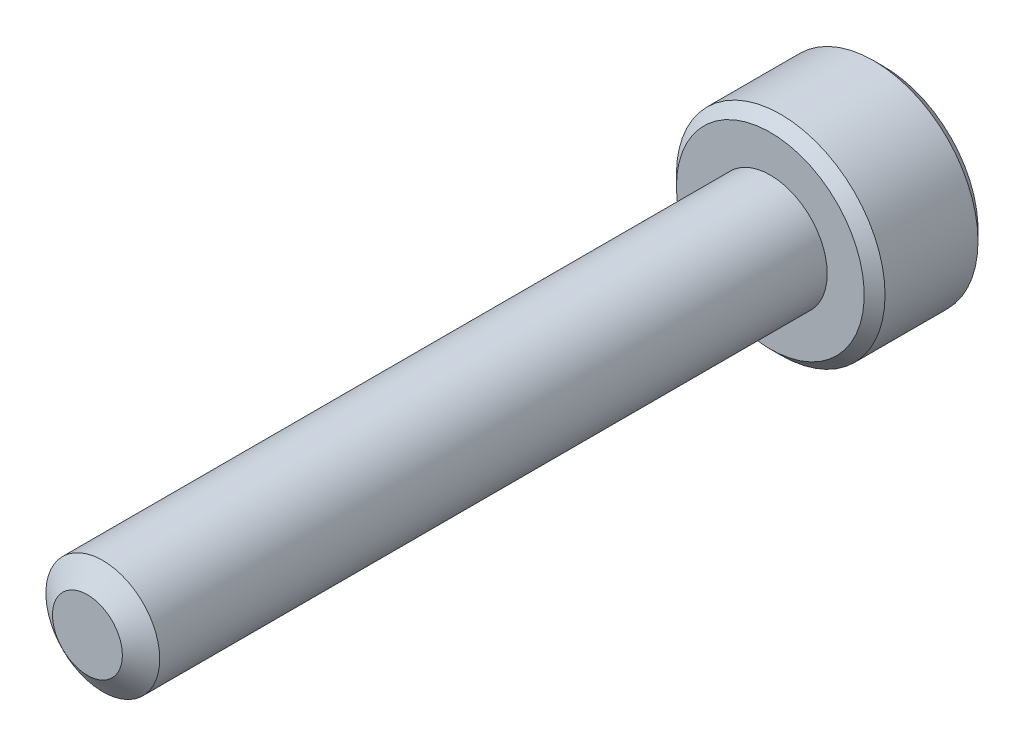
SolidWorks part; units mm, degrees
other "DetailItem1"
ref_plane "Front Plane" through (0, 0, 0) normal (0, 0, 1) x (1, 0, 0)
ref_plane "Top Plane" through (0, 0, 0) normal (0, 1, 0) x (1, 0, 0)
ref_plane "Right Plane" through (0, 0, 0) normal (1, 0, 0) x (0, 0, -1)
sketch "Sketch1" plane through (0, 0, 0) normal (0, 0, 1) x (1, 0, 0)
  circle A0 centre (0, 0) radius 1.5
  dimension "OD" = 3
extrude "Extrude1" add sketch "Sketch1" against normal blind 18
sketch "Sketch2" plane through (0, 0, 0) normal (0, 0, 1) x (1, 0, 0)
  circle A0 centre (0, 0) radius 1.5 construction
  circle A1 centre (0, 0) radius 1.5
curve "Helix/Spiral1" [suppressed] parameters "pitch"=0.5
sketch "Sketch3" plane through (0, 0, 0) normal (1, 0, 0) x (0, 0, -1)
  line L0 (-0.4375, 1.5) -> (-0.25, 1.1752)
  line L1 (-0.25, 1.1752) -> (-0.1875, 1.1752)
  line L2 (-0.1875, 1.1752) -> (0, 1.5)
  line L3 (-0.4375, 1.5) -> (0, 1.5)
  line L4 (-0.2187, 1.5) -> (-0.2188, 1.1752) construction
  line L5 (-0.3438, 1.3376) -> (-0.0938, 1.3376) construction
  line L6 (0, 1.5) -> (0, -1.5) construction
  dimension "D1" = 0.0625
  dimension "D2" = 0.25
  dimension "D3" = 60
sweep "Cut-Sweep1" [suppressed] cut profiles "Sketch3" path "Helix/Spiral1"
sketch "Sketch4" plane through (0, 0, 0) normal (1, 0, 0) x (0, 0, -1)
  line L0 (0.4053, 1.5) -> (0, 0.9212)
  line L1 (0, 0.9212) -> (0, 1.5)
  line L2 (0.4053, 1.5) -> (0, 1.5)
  line L3 (-0.4375, 1.5) -> (0, 1.5) construction
  line L4 (0, 0) -> (7.0209, 0) construction
  dimension "D1" = 55
  dimension "D2" = 0.254
revolve "Cut-Revolve1" cut sketch "Sketch4" angle 360 about L4
sketch "Sketch6" plane through (0, 0, -18) normal (0, 0, -1) x (-1, 0, 0)
  circle A0 centre (0, 0) radius 2.75
  dimension "head dia" = 5.5
extrude "Extrude2" add sketch "Sketch6" along normal blind 3
sketch "Sketch7" plane through (0, 0, -21) normal (0, 0, -1) x (-1, 0, 0)
  line L1 (0, 1.4434) -> (-1.25, 0.7217)
  line L2 (-1.25, 0.7217) -> (-1.25, -0.7217)
  line L3 (-1.25, -0.7217) -> (0, -1.4434)
  line L4 (0, -1.4434) -> (1.25, -0.7217)
  line L5 (1.25, -0.7217) -> (1.25, 0.7217)
  line L6 (1.25, 0.7217) -> (0, 1.4434)
  circle A0 centre (0, 0) radius 1.25 construction
  dimension "hex dia" = 2.5
extrude "Cut-Extrude1" cut sketch "Sketch7" against normal blind 1.875
sketch "Sketch8" plane through (0, 0, -21) normal (0, 0, -1) x (-1, 0, 0)
  circle A0 centre (0, 0) radius 1.4434
extrude "Cut-Extrude2" cut sketch "Sketch8" against normal through all draft 45
chamfer "Chamfer1" distance 0.275 angle 45 2 edges at (-2.75, 0, -21) (-2.75, 0, -18)
sketch "Sketch10" plane through (0, 0, -18) normal (0, 0, 1) x (1, 0, 0)
  circle A1 centre (0, 0) radius 1.5
  circle A2 centre (0, 0) radius 1.5
  dimension "D1" = 0
ref_plane "Plane1" through (0, 0, 0) normal (0, 0, 1) x (1, 0, 0)
extrude "partial thread" [suppressed] add sketch "Sketch10" along normal up to surface (4 mm away) separate body up to plane "Plane1"
chamfer "Chamfer2" [suppressed] distance 0.06 angle 45
combine bodies "Combine1" [suppressed] operation type add bodies to combine 107 108
sketch "Sketch9" plane through (0, 0, 0) normal (1, 0, 0) x (0, 0, -1)
  line L0 (0, 1.5) -> (0, -1.5) construction
  line L1 (1.25, 1.5) -> (1.25, -1.5) construction
  dimension "D1" = 1.25
equation "\"D3@Helix/Spiral1\" = \"screw length@Extrude1\"+\"pitch@Helix/Spiral1\""
equation "\"D1@Sketch3\" = \"pitch@Helix/Spiral1\"*.125"
equation "\"D2@Sketch3\" = \"pitch@Helix/Spiral1\"*.5"
equation "\"D1@Cut-Extrude1\" = \"hex dia@Sketch7\"*.75"
equation "\"D1@Chamfer1\" = \"head dia@Sketch6\"*.05"
equation "\"D1@Sketch9\" = \"pitch@Helix/Spiral1\"*2.5"
equation "\"D1@Chamfer2\"=\"OD@Sketch1\"*.02"
